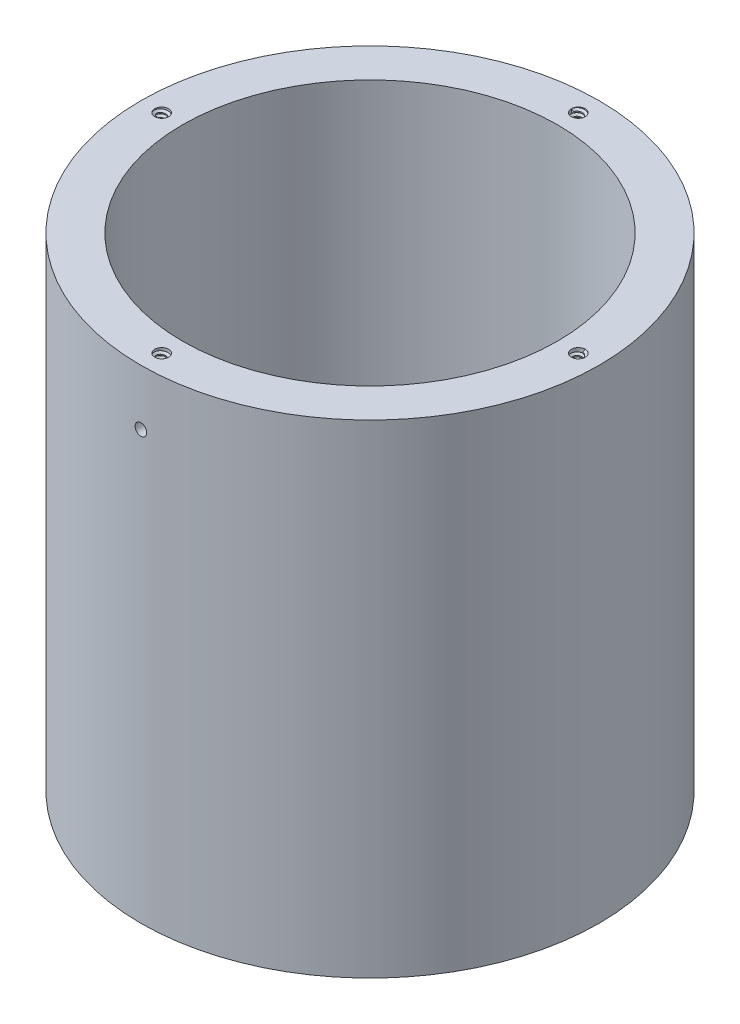
SolidWorks part; units mm, degrees
material "1060 Alloy"
ref_plane "Front Plane" through (0, 0, 0) normal (0, 0, 1) x (1, 0, 0)
ref_plane "Top Plane" through (0, 0, 0) normal (0, 1, 0) x (1, 0, 0)
ref_plane "Right Plane" through (0, 0, 0) normal (1, 0, 0) x (0, 0, -1)
sketch "Sketch1" plane through (0, 0, 0) normal (0, 1, 0) x (1, 0, 0)
  circle A0 centre (0, 0) radius 16.5
  circle A1 centre (0, 0) radius 13.5
  dimension "D1" = 33
  dimension "D2" = 27
extrude "Boss-Extrude1" add sketch "Sketch1" along normal blind 34.8
sketch "Sketch2" plane through (0, 34.8, 0) normal (0, 1, 0) x (1, 0, 0)
  circle A0 centre (0, 15) radius 0.5
  circle A2 centre (0, 0) radius 13.5 construction
  dimension "D1" = 1
  dimension "D2" = 15
extrude "Cut-Extrude1" cut sketch "Sketch2" against normal blind 2
thread "Thread1" pitch 0.3175 method extrude profile "Thread Profile1" start angle 0, offset 0, length 3.5, pitch 0.3175, diameter 1
ref_plane "Plane1" through (-0.5, 34.8, -15) normal (0, 0, 1) x (-1, 0, 0)
sketch "Thread Profile1" plane through (-0.5, 34.8, -15) normal (0, 0, 1) x (-1, 0, 0)
  line L0 (0, 0) -> (0, 0.3175) construction
  line L11 (0, 0) -> (0, 0.2778)
  line L12 (0, 0.2778) -> (-0.1719, 0.1786)
  line L13 (-0.1719, 0.1786) -> (-0.1719, 0.0992)
  line L15 (-0.1719, 0.0992) -> (0, 0)
  line L17 (-0.1719, 0.1389) -> (0, 0.1389) construction
  point P2 (0, 0)
  dimension "Pitch" = 0.3175
  dimension "Profile_Angle" = 60
  dimension "Profile_Land" = 0.0794
  dimension "Profile_Height" = 0.1719
pattern_circular "CirPattern1" count 4 over 360 about axis through (0, 34.8, 0) along (0, 1, 0) of "Cut-Extrude1", "Thread1"
sketch "Sketch5" plane through (0, 0, 0) normal (0, -1, 0) x (1, 0, 0)
  circle A0 centre (0, 15) radius 0.5
  dimension "D1" = 1
  dimension "D2" = 15
extrude "Cut-Extrude2" cut sketch "Sketch5" against normal blind 2
thread "Thread2" pitch 0.3175 method extrude profile "Thread Profile2" start angle 0, offset 0, length 3.5, pitch 0.3175, diameter 1
ref_plane "Plane2" through (0.5, 0, 15) normal (0, 0, 1) x (1, 0, 0)
sketch "Thread Profile2" plane through (0.5, 0, 15) normal (0, 0, 1) x (1, 0, 0)
  line L0 (0, 0) -> (0, 0.3175) construction
  line L11 (0, 0) -> (0, 0.2778)
  line L12 (0, 0.2778) -> (-0.1719, 0.1786)
  line L13 (-0.1719, 0.1786) -> (-0.1719, 0.0992)
  line L15 (-0.1719, 0.0992) -> (0, 0)
  line L17 (-0.1719, 0.1389) -> (0, 0.1389) construction
  point P2 (0, 0)
  dimension "Pitch" = 0.3175
  dimension "Profile_Angle" = 60
  dimension "Profile_Land" = 0.0794
  dimension "Profile_Height" = 0.1719
pattern_circular "CirPattern2" count 4 over 360 about axis through (0, 0, 0) along (0, 1, 0) of "Cut-Extrude2", "Thread2"
sketch "Sketch6" plane through (0, 0, 0) normal (0, 0, 1) x (1, 0, 0)
  line L0 (16.5, 34.8) -> (-16.5, 34.8) construction
  circle A0 centre (0, 30.8) radius 0.42
  dimension "D1" = 0.84
  dimension "D2" = 4
extrude "Cut-Extrude4" cut sketch "Sketch6" along normal blind 20
